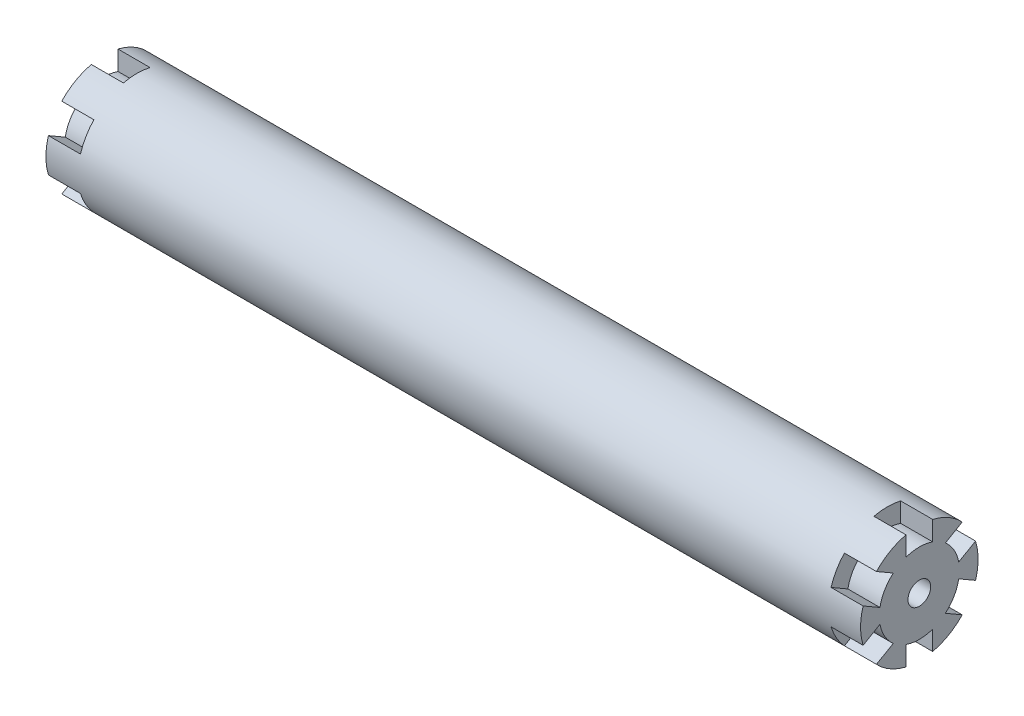
SolidWorks part; units mm, degrees
ref_plane "Front Plane" through (0, 0, 0) normal (0, 0, 1) x (1, 0, 0)
ref_plane "Top Plane" through (0, 0, 0) normal (0, 1, 0) x (1, 0, 0)
ref_plane "Right Plane" through (0, 0, 0) normal (1, 0, 0) x (0, 0, -1)
sketch "Sketch1" plane through (0, 0, 0) normal (1, 0, 0) x (0, 0, -1)
  circle A0 centre (0, 0) radius 22
  circle A1 centre (0, 0) radius 4.25
  dimension "D1" = 44
  dimension "D2" = 8.5
extrude "Boss-Extrude1" add sketch "Sketch1" along normal blind 305
sketch "Sketch2" plane through (0, 0, 0) normal (-1, 0, 0) x (0, 0, 1)
  line L0 (0, 0) -> (0, 27.2309) construction
  line L1 (14.7474, 2.7409) -> (21.054, 6.382)
  line L3 (5, 14.1421) -> (5, 21.4243)
  line L5 (-5, 14.1421) -> (-5, 21.4243)
  line L6 (9.7474, 11.4012) -> (16.054, 15.0423)
  line L7 (9.7474, -11.4012) -> (16.054, -15.0423)
  line L8 (14.7474, -2.7409) -> (21.054, -6.382)
  line L9 (-5, -14.1421) -> (-5, -21.4243)
  line L10 (5, -14.1421) -> (5, -21.4243)
  line L11 (-14.7474, -2.7409) -> (-21.054, -6.382)
  line L12 (-9.7474, -11.4012) -> (-16.054, -15.0423)
  line L13 (-9.7474, 11.4012) -> (-16.054, 15.0423)
  line L14 (-14.7474, 2.7409) -> (-21.054, 6.382)
  circle A0 centre (0, 0) radius 15
  circle A1 centre (0, 0) radius 22 construction
  circle A2 centre (0, 0) radius 22
  point P33 (0, 0)
  circle M2 centre (0, 0) radius 22
  dimension "D1" = 30
  dimension "D2" = 10
  dimension "D3" = 6
extrude "Cut-Extrude1" cut sketch "Sketch2" against normal blind 12 contours A0 L1 L6 M2 | A0 L7 L8 M2 | A0 L9 L10 M2 | A0 L11 L12 M2 | A0 L13 L14 M2 | L0 A0 L3 M2 | A0 L0 A2 L5 region at (0, 18.2608, -2.5164) region at (0, 18.2608, 2.5164) region at (0, 9.1304, 15.8143) region at (0, 9.1304, -15.8143) region at (0, -9.1304, -15.8143) region at (0, -9.1304, 15.8143) region at (0, -18.2608, 0)
extrude "Cut-Extrude2" cut sketch "Sketch2<4>" along normal blind 12 from surface contours A0 L1 L6 M2 | L0 A0 L3 M2 | A0 L0 A2 L5 | A0 L13 L14 M2 | A0 L11 L12 M2 | A0 L9 L10 M2 | A0 L7 L8 M2 region at (0, 18.2608, -2.5164) region at (0, 18.2608, 2.5164) region at (0, 9.1304, 15.8143) region at (0, 9.1304, -15.8143) region at (0, -9.1304, -15.8143) region at (0, -9.1304, 15.8143) region at (0, -18.2608, 0) starting at face at (305, 0, -22)
sketch "Sketch2<4>" plane through (0, 0, 0) normal (-1, 0, 0) x (0, 0, 1) same geometry as "Sketch2"
